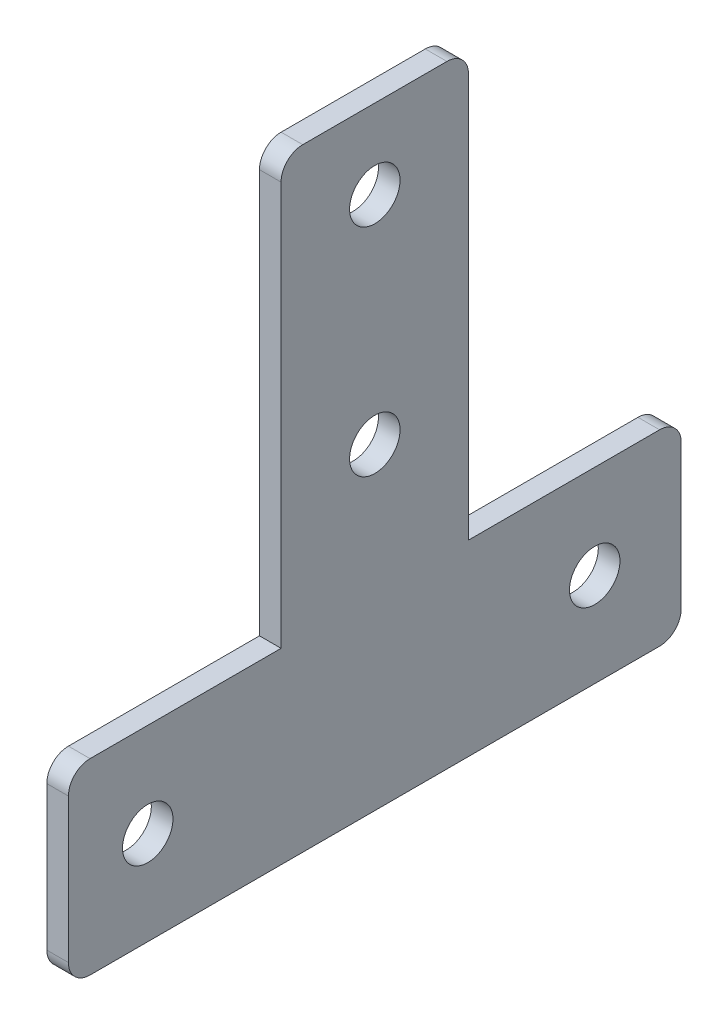
SolidWorks part; units mm, degrees
note: '?' marks a value the reader was unsure of.
ref_plane "Front Plane" through (0, 0, 0) normal (0, 0, 1) x (1, 0, 0)
ref_plane "Top Plane" through (0, 0, 0) normal (0, 1, 0) x (1, 0, 0)
ref_plane "Right Plane" through (0, 0, 0) normal (1, 0, 0) x (0, 0, -1)
ref_axis "Axis_X" through (-88.99, 0, 0) along (1, 0, 0)?
ref_axis "Axis_Y" through (0, 55, 0) along (0, -1, 0)?
ref_axis "Axis_Z" through (0, 0, -88.99) along (0, 0, 1)?
sketch "Sketch1" plane through (0, 0, 0) normal (1, 0, 0) x (0, 0, -1)
  line L1 (0, 0) -> (85, 0)
  line L2 (0, 0) -> (0, 85)
  line L3 (0, 85) -> (85, 85)
  line L4 (85, 0) -> (85, 85)
  line L5 (0, 0) -> (85, 85) construction
  line L6 (0, 85) -> (85, 0) construction
  point P0 (0, 0)
  dimension "L" = 85
extrude "Boss-Extrude1" add sketch "Sketch1" along normal blind 3
sketch "Sketch2" plane through (0, 0, 0) normal (1, 0, 0) x (0, 0, -1)
  line L0 (26, 85) -> (26, 26)
  line L1 (85, 85) -> (0, 85) construction
  line L2 (26, 26) -> (85, 26)
  line L3 (0, 85) -> (0, 0) construction
  line L4 (85, 0) -> (85, 85) construction
  line L5 (85, 26) -> (85, 85)
  line L6 (85, 85) -> (26, 85)
  dimension "H" = 59
  dimension "W" = 26
extrude "Cut-Extrude1" [suppressed] cut sketch "Sketch2" along normal through all
hole_wizard "DiameterHole1" [suppressed] positions "Sketch4" profile "Sketch3" hole size "Ø7.0" standard "JIS"
sketch "Sketch4" plane through (3, 0, 0) normal (1, 0, 0) x (0, 0, -1)
  line L0 (42.5, 85) -> (42.5, 0) construction
  line L1 (85, 85) -> (0, 85) construction
  line L2 (0, 0) -> (85, 0) construction
  line L4 (85, 42.5) -> (0, 42.5) construction
  line L5 (85, 0) -> (85, 85) construction
  line L6 (0, 85) -> (0, 0) construction
  point P0 (42.5, 74)
  point P2 (42.5, 44)
  point P4 (74, 42.5)
  point P6 (44, 42.5)
sketch "Sketch3" plane through (3, 74, -42.5) normal (0, 1, 0) x (0, 0, -1)
  line L0 (0, 0) -> (0, 3)
  line L1 (0, 3) -> (3.5, 3)
  line L2 (3.5, 3) -> (3.5, 0)
  line L5 (3.5, 0) -> (0, 0)
  line L11 (0, -6.35) -> (0, 107.95) construction
  dimension "D" = 7
  dimension "Thru Hole Depth" = 3
sketch "Sketch5" plane through (0, 0, 0) normal (1, 0, 0) x (0, 0, -1)
  line L0 (42.5, 0) -> (42.5, 85) construction
  line L1 (0, 0) -> (85, 0) construction
  line L3 (0, 85) -> (29.5, 85)
  line L4 (85, 85) -> (0, 85) construction
  line L5 (29.5, 85) -> (29.5, 26)
  line L7 (29.5, 26) -> (0, 26)
  line L8 (0, 85) -> (0, 0) construction
  line L9 (0, 26) -> (0, 85)
  line L10 (85, 26) -> (85, 85)
  line L11 (55.5, 26) -> (85, 26)
  line L12 (85, 85) -> (0, 85) construction
  line L13 (55.5, 85) -> (55.5, 26)
  line L14 (85, 85) -> (55.5, 85)
  dimension "W" = 26
  dimension "H" = 59
extrude "Cut-Extrude2" cut sketch "Sketch5" along normal through all
hole_wizard "DiameterHole2" positions "Sketch7" profile "Sketch6" hole size "Ø7.0" standard "JIS" end condition through all
sketch "Sketch7" plane through (3, 0, 0) normal (1, 0, 0) x (0, 0, -1)
  line L0 (42.5, 85) -> (42.5, 0) construction
  line L1 (55.5, 85) -> (29.5, 85) construction
  line L2 (0, 0) -> (85, 0) construction
  line L4 (0, 13) -> (85, 13) construction
  line L5 (0, 26) -> (0, 0) construction
  line L6 (85, 0) -> (85, 26) construction
  point P0 (42.5, 74)
  point P2 (42.5, 44)
  point P4 (11, 13)
  point P6 (73, 13)
  dimension "L2" = 30
  dimension "L1" = 62
sketch "Sketch6" plane through (3, 74, -42.5) normal (0, 1, 0) x (0, 0, -1)
  line L0 (0, 0) -> (0, 3)
  line L1 (0, 3) -> (3.5, 3)
  line L2 (3.5, 3) -> (3.5, 0)
  line L5 (3.5, 0) -> (0, 0)
  line L11 (0, -6.35) -> (0, 107.95) construction
  dimension "D" = 7
  dimension "Thru Hole Depth" = 3
fillet "Fillet1" [suppressed] radius 3
fillet "Fillet2" radius 3 6 edges at (1.5, 0, -85) (1.5, 0, 0) (1.5, 26, -85) (1.5, 26, 0) (1.5, 85, -55.5) (1.5, 85, -29.5)
equation "\"Factor\"= 1.082532"
